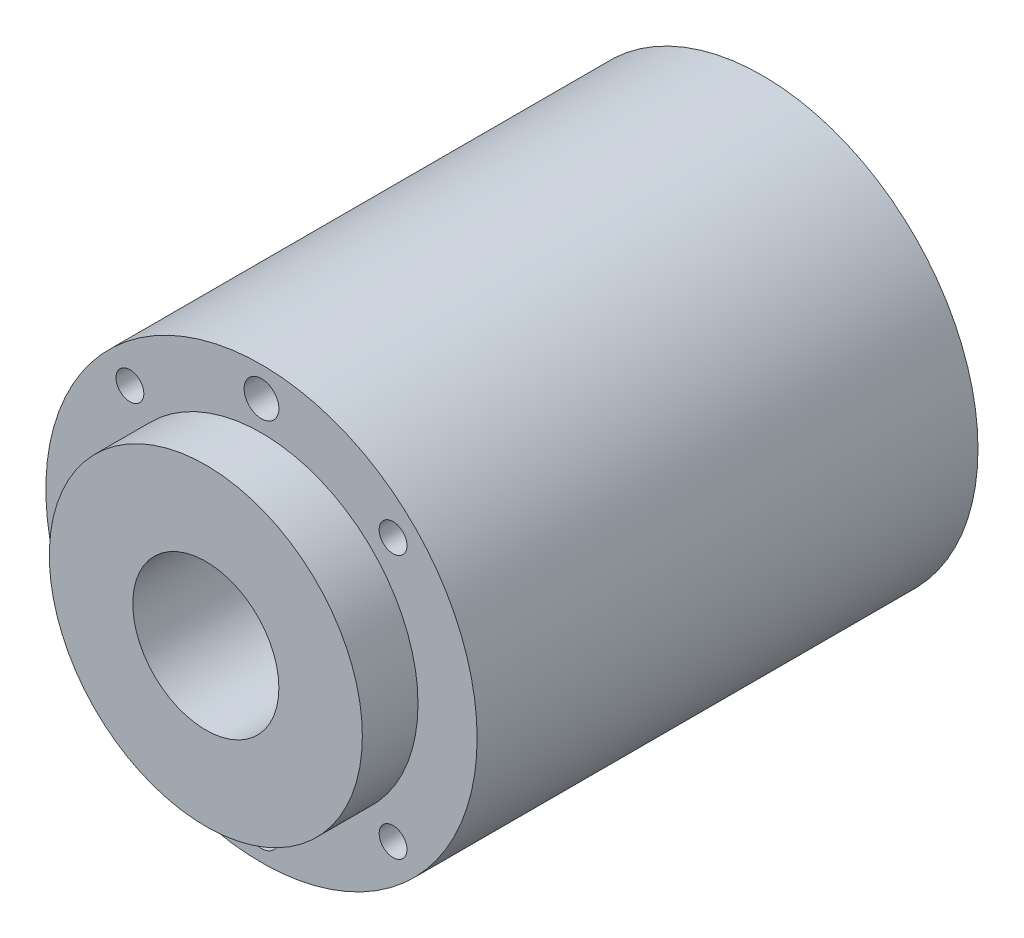
SolidWorks part; units mm, degrees
material "6061 合金"
ref_plane "前视基准面" through (0, 0, 0) normal (0, 0, 1) x (1, 0, 0)
ref_plane "上视基准面" through (0, 0, 0) normal (0, 1, 0) x (1, 0, 0)
ref_plane "右视基准面" through (0, 0, 0) normal (1, 0, 0) x (0, 0, -1)
sketch "草图1" plane through (0, 0, 0) normal (0, 0, 1) x (1, 0, 0)
  circle A0 centre (0, 0) radius 22.5
  circle A1 centre (0, 0) radius 31
  circle A2 centre (0, 0) radius 10.5
  dimension "D1" = 45
  dimension "D2" = 62
  dimension "D3" = 21
extrude "凸台-拉伸1" add sketch "草图1" against normal blind 72 contours A1 A0 | A0 A2 region at (-21.8636, 0, 0) region at (-30.1232, 0, 0)
extrude "凸台-拉伸2" add sketch "草图1<3>" along normal blind 8 contours A0 A2 region at (-21.8636, 0, 0)
sketch "草图1<3>" plane through (0, 0, 0) normal (0, 0, 1) x (1, 0, 0) same geometry as "草图1"
sketch "草图2" plane through (0, 0, 0) normal (0, 0, 1) x (1, 0, 0)
  line L0 (0, 26.75) -> (0, 0) construction
  line L1 (0, 0) -> (26.75, 0) construction
  line L2 (18.9151, 18.9151) -> (0, 0) construction
  circle A0 centre (0, 0) radius 26.75 construction
  circle A1 centre (0, 26.75) radius 2.5
  circle A2 centre (18.9151, 18.9151) radius 2
  circle A3 centre (0, -26.75) radius 2.5
  circle A4 centre (18.9151, -18.9151) radius 2
  circle A5 centre (-18.9151, -18.9151) radius 2
  circle A6 centre (-18.9151, 18.9151) radius 2
  point P19 (0, 0)
  dimension "D1" = 53.5
  dimension "D2" = 5
  dimension "D3" = 4
  dimension "D4" = 45
  dimension "D5" = 4
extrude "切除-拉伸3" cut sketch "草图2" against normal blind 7
cosmetic thread "装饰螺纹线1" parameters "D2"=5
cosmetic thread "装饰螺纹线2" parameters "D2"=5
cosmetic thread "装饰螺纹线3" parameters "D2"=5
cosmetic thread "装饰螺纹线4" parameters "D2"=5
ref_point "J6末端"
